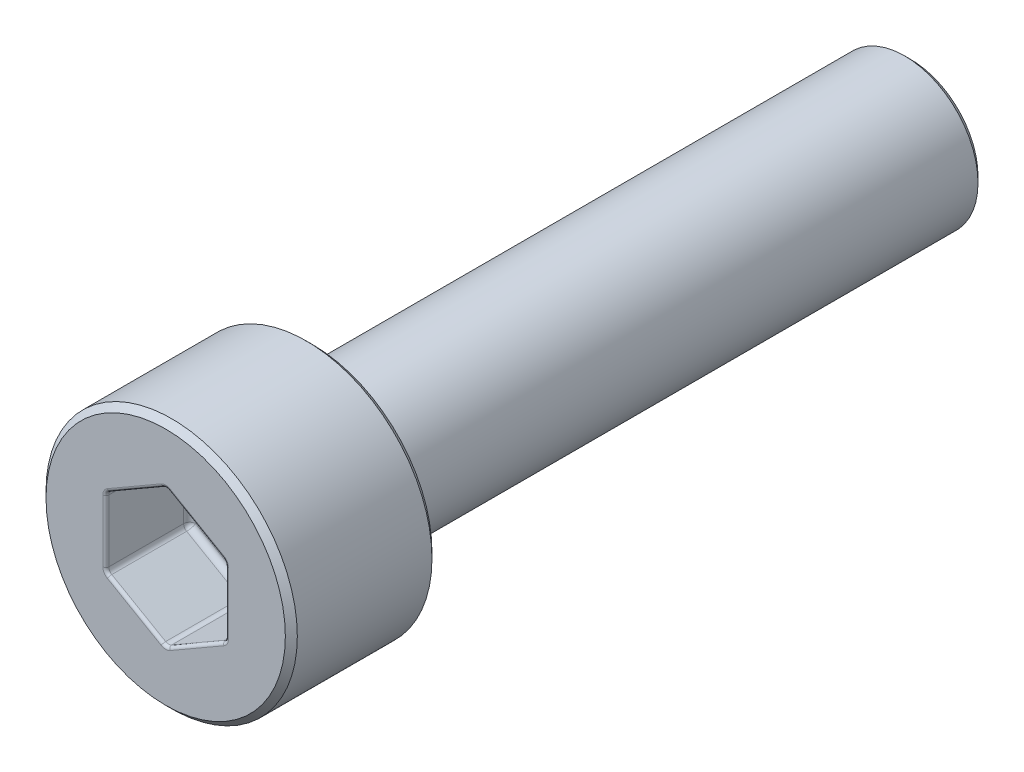
SolidWorks part; units mm, degrees
material "1.4000 (X6Cr13)"
ref_plane "Ebene vorne" through (0, 0, 0) normal (0, 0, 1) x (1, 0, 0)
ref_plane "Ebene oben" through (0, 0, 0) normal (0, 1, 0) x (1, 0, 0)
ref_plane "Ebene rechts" through (0, 0, 0) normal (1, 0, 0) x (0, 0, -1)
sketch "Skizze1" plane through (0, 0, 0) normal (1, 0, 0) x (0, 0, -1)
  line L0 (-21.9199, 0) -> (33.7608, 0) construction
  line L1 (0, 13.9907) -> (0, -9.4798) construction
  line L2 (-4.9, 0) -> (-4.9, 4.2)
  line L3 (-4.9, 4.2) -> (0, 4.2)
  line L4 (0, 4.2) -> (0, 2.45)
  line L5 (0, 2.45) -> (20, 2.45)
  line L6 (20, 2.45) -> (20, 0)
  line L7 (20, 0) -> (-4.9, 0)
  dimension "D1" = 4.9
  dimension "D2" = 4.9
  dimension "D3" = 8.4
  dimension "D4" = 20
revolve "Rotation1" add sketch "Skizze1" angle 360 about L0
sketch "Skizze2" plane through (0, 0, 4.9) normal (0, 0, 1) x (1, 0, 0)
  line L0 (0, 8.6995) -> (0, -7.3778) construction
  line L1 (2, -1.1547) -> (2, 1.1547)
  line L2 (2, 1.1547) -> (0, 2.3094)
  line L3 (0, 2.3094) -> (-2, 1.1547)
  line L4 (-2, 1.1547) -> (-2, -1.1547)
  line L5 (-2, -1.1547) -> (0, -2.3094)
  line L6 (0, -2.3094) -> (2, -1.1547)
  circle A0 centre (0, 0) radius 2 construction
  dimension "D1" = 4
extrude "Schnitt-Linear austragen1" cut sketch "Skizze2" against normal blind 2.8
chamfer "Fase1" distance 0.2 angle 45 3 edges at (4.2, 0, 4.9) (4.2, 0, 0) (2.45, 0, -20)
fillet "Verrundung1" radius 0.2 13 edges at (-1, -1.7321, 2.1) (-2, 0, 2.1) (-1, 1.7321, 2.1) (1, 1.7321, 2.1) (2, 0, 2.1) (1, -1.7321, 2.1) (-2, -1.1547, 3.5) (0, -2.3094, 3.5) (2, -1.1547, 3.5) (2, 1.1547, 3.5) (0, 2.3094, 3.5) (-2, 1.1547, 3.5) (2.45, 0, 0)
fillet "Verrundung2" radius 0.1 12 edges at (1.9732, -1.1392, 4.9) (1, -1.7321, 4.9) (0, -2.2785, 4.9) (-1, -1.7321, 4.9) (-1.9732, -1.1392, 4.9) (-2, 0, 4.9) (-1.9732, 1.1392, 4.9) (-1, 1.7321, 4.9) (0, 2.2785, 4.9) (1, 1.7321, 4.9) (1.9732, 1.1392, 4.9) (2, 0, 4.9)
ref_axis "Achse1" through (0, 0, -19.6323) along (0, 0, 1)
